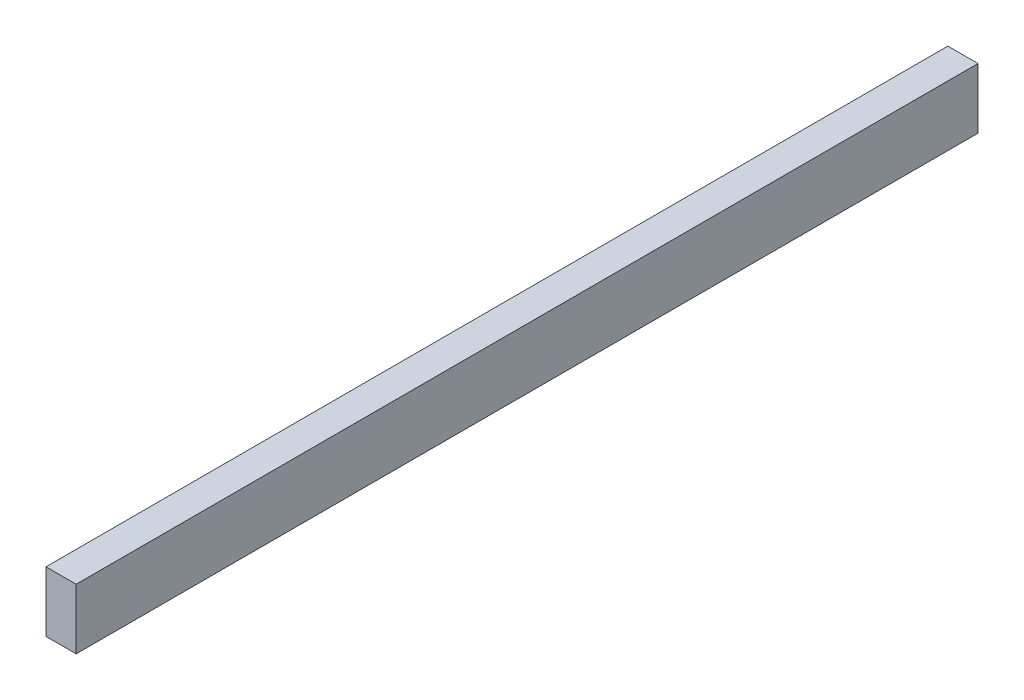
SolidWorks part; units mm, degrees
material "SPF Select 2Btr Grade Lumber"
ref_plane "Front Plane" through (0, 0, 0) normal (0, 0, 1) x (1, 0, 0)
ref_plane "Top Plane" through (0, 0, 0) normal (0, 1, 0) x (1, 0, 0)
ref_plane "Right Plane" through (0, 0, 0) normal (1, 0, 0) x (0, 0, -1)
sketch "Sketch1" plane through (0, 0, 0) normal (0, 0, 1) x (1, 0, 0)
  line L1 (0, 0) -> (50.8, 0)
  line L2 (0, 0) -> (0, 101.6)
  line L3 (0, 101.6) -> (50.8, 101.6)
  line L4 (50.8, 0) -> (50.8, 101.6)
  dimension "D1" = 50.8
  dimension "D2" = 101.6
extrude "Boss-Extrude1" add sketch "Sketch1" along normal blind 1518.68
